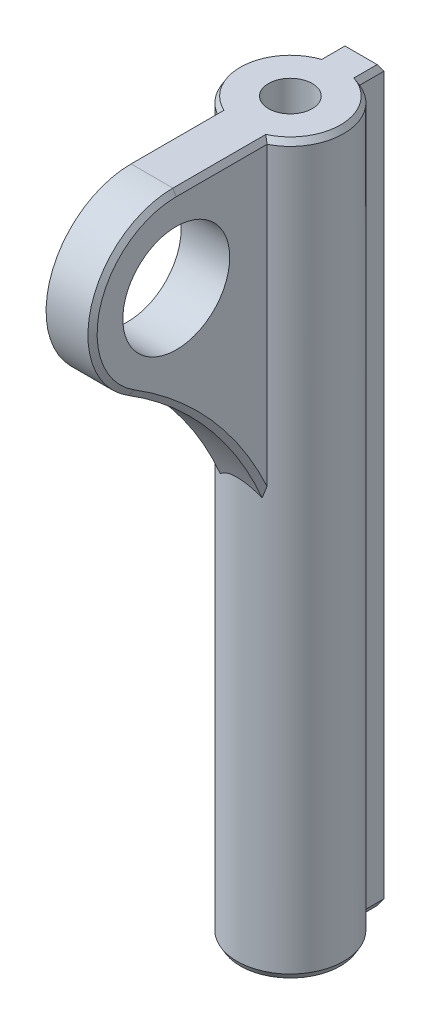
SolidWorks part; units mm, degrees
ref_plane "정면" through (0, 0, 0) normal (0, 0, 1) x (1, 0, 0)
ref_plane "윗면" through (0, 0, 0) normal (0, 1, 0) x (1, 0, 0)
ref_plane "우측면" through (0, 0, 0) normal (1, 0, 0) x (0, 0, -1)
sketch "스케치1" plane through (0, 0, 0) normal (0, 1, 0) x (1, 0, 0)
  line L0 (0, 0) -> (0, 12.747) construction
  line L2 (4, 15.247) -> (-4, 15.247)
  line L3 (4, 15.247) -> (4, 10.247)
  line L4 (4, 10.247) -> (-4, 10.247) construction
  line L5 (-4, 15.247) -> (-4, 10.247)
  line L6 (4, 15.247) -> (-4, 10.247) construction
  line L7 (4, 10.247) -> (-4, 15.247) construction
  circle A0 centre (0, 0) radius 11
  dimension "D1" = 22
  dimension "D2" = 8
  dimension "D3" = 5
extrude "보스-돌출1" add sketch "스케치1" along normal mid plane 150 contours A0 L3 L2 L5 | A0 region at (0, 0, -12.9942)
sketch "스케치2" plane through (0, 0, 0) normal (0, 1, 0) x (1, 0, 0)
  circle A0 centre (0, 0) radius 4.5
  dimension "D1" = 9
extrude "컷-돌출1" cut sketch "스케치2" against normal through all both and the other way through all
sketch "스케치5" plane through (0, -75, 0) normal (0, -1, 0) x (1, 0, 0)
  circle A0 centre (0, 0) radius 8 construction
  circle A1 centre (0, 8) radius 1.3
  circle A2 centre (8, 0) radius 1.3
  circle A3 centre (0, -8) radius 1.3
  circle A4 centre (-8, 0) radius 1.3
  dimension "D1" = 16
  dimension "D2" = 2.6
extrude "컷-돌출4" cut sketch "스케치5" against normal blind 36
sketch "스케치6" plane through (0, -75, 0) normal (0, -1, 0) x (1, 0, 0)
  circle A0 centre (0, 0) radius 5.2
  dimension "D1" = 10.4
extrude "컷-돌출5" cut sketch "스케치6" against normal blind 11
sketch "스케치7" plane through (0, 0, 0) normal (1, 0, 0) x (0, 0, -1)
  line L1 (-11, 75) -> (-11, -75) construction
  line L4 (-28.5, 75) -> (-4.5, 75)
  line L5 (-11, 57.5) -> (-4.5, 57.5) construction
  line L6 (10.247, 75) -> (-11, 75) construction
  line L8 (-4.5, -16.9329) -> (-4.5, 75)
  circle A0 centre (-28.5, 57.5) radius 17.5
  circle A1 centre (-28.5, 57.5) radius 11
  arc A2 (-37.7, 42.6134) -> (-4.5, -16.9329) centre (-74.5, -16.9329) cw
  dimension "D1" = 35
  dimension "D2" = 6.5
  dimension "D4" = 70
  dimension "D3" = 6.5
extrude "보스-돌출6" add sketch "스케치7" along normal mid plane 10 contours L5 A0 A2 L8 | A0 L5 L8 L4 | A0 A1 region at (0, 68.0228, 10.3716) region at (0, 69.5244, 16.4756) region at (0, 31.8984, 12.2676)
chamfer "모따기1" distance 1.2 angle 30 11 edges at (5, 28.3976, 21.16) (-5, 28.3976, 21.16) (5, 62.282, 45.334) (-5, 62.282, 45.334) (5, 75, 19.149) (10.9863, 75, -0.5481) (4, 75, -12.747) (0, 75, -15.247) (-4, 75, -12.747) (-5, 75, 19.149) (-10.9863, 75, -0.5481) first distance on face at (5, 57.5, 17.5) first distance on face at (-5, 57.5, 17.5) first distance on face at (0.0052, 21.5382, 2.5007) first distance on face at (4, 0, -12.747) first distance on face at (0, 0, -15.247) first distance on face at (-4, 0, -12.747)
chamfer "모따기2" distance 1.2 angle 30 4 edges at (-4, -75, -12.747) (0, -75, -15.247) (4, -75, -12.747) (0, -75, 11) first distance on face at (-4, -0.6, -12.747) first distance on face at (0, -0.6, -15.247) first distance on face at (4, -0.6, -12.747) first distance on face at (0.0734, 19.3845, 3.9925)
